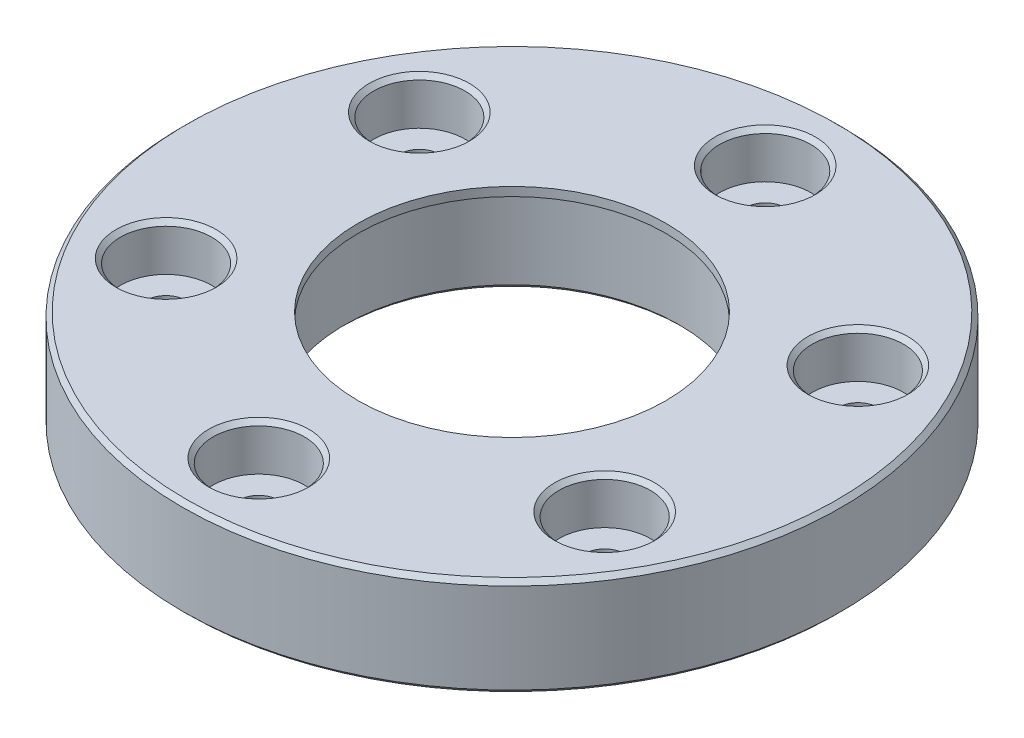
SolidWorks part; units mm, degrees
ref_plane "前视基准面" through (0, 0, 0) normal (0, 0, 1) x (1, 0, 0)
ref_plane "上视基准面" through (0, 0, 0) normal (0, 1, 0) x (1, 0, 0)
ref_plane "右视基准面" through (0, 0, 0) normal (1, 0, 0) x (0, 0, -1)
other "Configuration Table"
sketch "草图1" plane through (0, 0, 0) normal (0, 1, 0) x (1, 0, 0)
  circle A0 centre (0, 0) radius 7
  circle A1 centre (0, 0) radius 15
  circle A2 centre (0, 0) radius 11.525 construction
  circle A3 centre (0, 11.525) radius 2.08
  circle A4 centre (9.9809, 5.7625) radius 2.08
  circle A5 centre (9.9809, -5.7625) radius 2.08
  circle A6 centre (0, -11.525) radius 2.08
  circle A7 centre (-9.9809, -5.7625) radius 2.08
  circle A8 centre (-9.9809, 5.7625) radius 2.08
  point P19 (0, 0)
  dimension "D1" = 14
  dimension "D2" = 30
  dimension "D3" = 23.05
  dimension "D4" = 4.16
  dimension "D5" = 6
extrude "凸台-拉伸1" add sketch "草图1" along normal blind 2.1
sketch "草图2" plane through (0, 0, 0) normal (0, -1, 0) x (-1, 0, 0)
  circle A0 centre (0, 0) radius 7 construction
  circle A1 centre (0, 0) radius 15 construction
  circle A2 centre (0, 0) radius 7
  circle A3 centre (0, 0) radius 15
  circle A4 centre (0, 11.53) radius 0.9
  circle A6 centre (0, 0) radius 11.53 construction
  circle A7 centre (9.9853, 5.765) radius 0.9
  circle A8 centre (9.9853, -5.765) radius 0.9
  circle A9 centre (0, -11.53) radius 0.9
  circle A10 centre (-9.9853, -5.765) radius 0.9
  circle A11 centre (-9.9853, 5.765) radius 0.9
  point P21 (0, 0)
  dimension "D1" = 1.8
  dimension "D2" = 23.06
  dimension "D3" = 6
extrude "凸台-拉伸2" add sketch "草图2" along normal blind 2.4
sketch "草图3" plane through (0, -2.4, 0) normal (0, -1, 0) x (-1, 0, 0)
  circle A0 centre (0, 0) radius 7.6
  dimension "D1" = 15.2
extrude "切除-拉伸1" cut sketch "草图3" against normal blind 4.1
chamfer "倒角1" distance 0.2 angle 45 15 edges at (0, -2.4, -15) (-9.9809, 2.1, -3.6825) (0, 2.1, 13.605) (9.9809, 2.1, -3.6825) (0, 2.1, 15) (0, 2.1, -9.445) (9.9809, 2.1, 7.8425) (-9.9809, 2.1, 7.8425) (9.9853, -2.4, -6.665) (0, -2.4, 10.63) (-9.9853, -2.4, -6.665) (0, -2.4, -12.43) (-9.9853, -2.4, 4.865) (9.9853, -2.4, 4.865) (0, -2.4, -7.6)
chamfer "倒角2" distance 0.3 angle 45 1 edges at (0, 1.7, -7.6)
